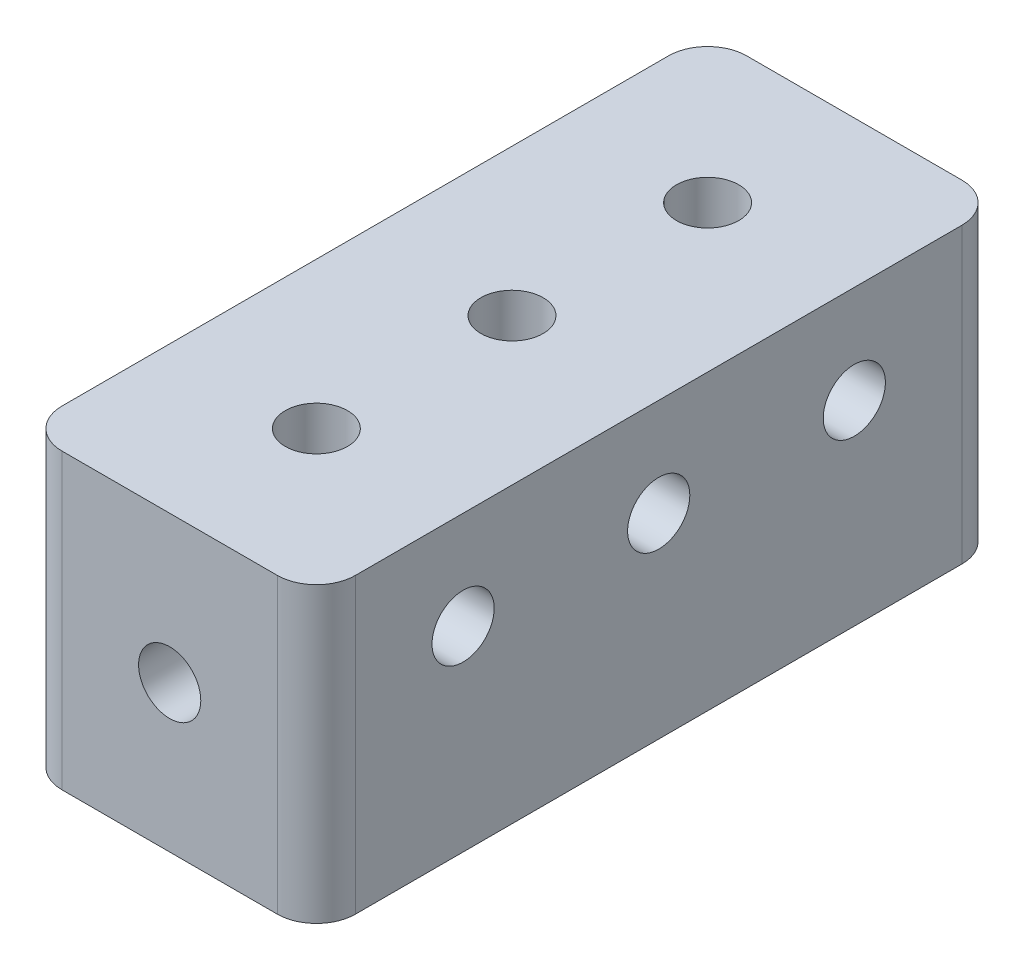
SolidWorks part; units mm, degrees
material "6061-T6 (SS)"
ref_plane "Front Plane" through (0, 0, 0) normal (0, 0, 1) x (1, 0, 0)
ref_plane "Top Plane" through (0, 0, 0) normal (0, 1, 0) x (1, 0, 0)
ref_plane "Right Plane" through (0, 0, 0) normal (1, 0, 0) x (0, 0, -1)
sketch "Sketch1" plane through (0, 0, 0) normal (0, 1, 0) x (1, 0, 0)
  line L1 (-9.525, -22.225) -> (9.525, -22.225)
  line L2 (-9.525, -22.225) -> (-9.525, 22.225)
  line L3 (-9.525, 22.225) -> (9.525, 22.225)
  line L4 (9.525, -22.225) -> (9.525, 22.225)
  line L5 (-9.525, -22.225) -> (9.525, 22.225) construction
  line L6 (-9.525, 22.225) -> (9.525, -22.225) construction
  point P0 (0, 0)
  dimension "D1" = 19.05
  dimension "D2" = 44.45
extrude "Boss-Extrude1" add sketch "Sketch1" along normal mid plane 19.05
sketch "Sketch2" plane through (0, 0, 22.225) normal (0, 0, 1) x (1, 0, 0)
  circle A0 centre (0, 0) radius 2.0193
  dimension "D3" = 4.0386
extrude "Cut-Extrude1" cut sketch "Sketch2" against normal blind 9.525
sketch "Sketch3" plane through (0, 0, -22.225) normal (0, 0, -1) x (-1, 0, 0)
  circle A0 centre (0, 0) radius 2.0193 construction
  circle A1 centre (0, 0) radius 2.0193
extrude "Cut-Extrude2" cut sketch "Sketch3" against normal through all
sketch "Sketch4" plane through (9.525, 0, 0) normal (1, 0, 0) x (0, 0, -1)
  line L0 (-22.225, 9.525) -> (22.225, 9.525) construction
  circle A0 centre (-12.7, 3.175) radius 2.0193
  circle A1 centre (12.7, 3.175) radius 2.0193
  circle A2 centre (0, 3.175) radius 2.0193
  dimension "D5" = 4.0386
  dimension "D1" = 6.35
  dimension "D3" = 12.7
  dimension "D4" = 12.7
extrude "Cut-Extrude3" cut sketch "Sketch4" against normal blind 6.35
sketch "Sketch5" plane through (-9.525, 0, 0) normal (-1, 0, 0) x (0, 0, 1)
  circle A0 centre (-12.7, 3.175) radius 2.0193 construction
  circle A1 centre (0, 3.175) radius 2.0193 construction
  circle A2 centre (12.7, 3.175) radius 2.0193 construction
  circle A3 centre (-12.7, 3.175) radius 2.0193
  circle A4 centre (0, 3.175) radius 2.0193
  circle A5 centre (12.7, 3.175) radius 2.0193
extrude "Cut-Extrude4" cut sketch "Sketch5" against normal blind 6.35
sketch "Sketch6" plane through (0, 9.525, 0) normal (0, 1, 0) x (1, 0, 0)
  circle A0 centre (0, 12.7) radius 2.0193
  circle A1 centre (0, 0) radius 2.0193
  circle A2 centre (0, -12.7) radius 2.0193
  dimension "D1" = 4.0386
  dimension "D2" = 12.7
  dimension "D3" = 12.7
extrude "Cut-Extrude5" cut sketch "Sketch6" against normal blind 6.35
fillet "Fillet1" radius 2.54 4 edges at (9.525, 0, 22.225) (-9.525, 0, 22.225) (-9.525, 0, -22.225) (9.525, 0, -22.225)
